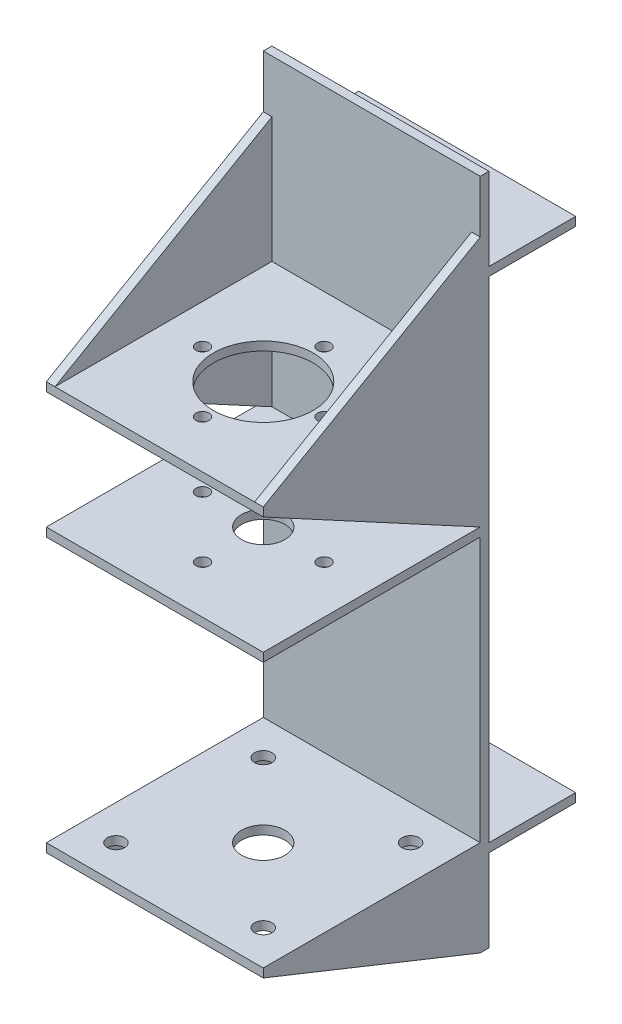
SolidWorks part; units mm, degrees
ref_plane "Front Plane" through (0, 0, 0) normal (0, 0, 1) x (1, 0, 0)
ref_plane "Top Plane" through (0, 0, 0) normal (0, 1, 0) x (1, 0, 0)
ref_plane "Right Plane" through (0, 0, 0) normal (1, 0, 0) x (0, 0, -1)
sketch "Sketch1" plane through (0, 0, 0) normal (0, 0, 1) x (1, 0, 0)
  line L1 (-25, 77.5) -> (25, 77.5)
  line L2 (-25, 77.5) -> (-25, -77.5)
  line L3 (-25, -77.5) -> (25, -77.5)
  line L4 (25, 77.5) -> (25, -77.5)
  line L5 (-25, 77.5) -> (25, -77.5) construction
  line L6 (-25, -77.5) -> (25, 77.5) construction
  point P0 (0, 0)
  point P5 (0, 0)
  point P7 (0, 0)
  dimension "D1" = 155
  dimension "D2" = 50
extrude "Boss-Extrude1" add sketch "Sketch1" along normal blind 2
sketch "Sketch2" plane through (0, 0, 2) normal (0, 0, 1) x (1, 0, 0)
  line L0 (-25, 77.5) -> (-25, -77.5) construction
  line L1 (-25, -57.5) -> (25, -57.5)
  line L2 (-25, -57.5) -> (-25, -55.5)
  line L3 (-25, -55.5) -> (25, -55.5)
  line L4 (25, -57.5) -> (25, -55.5)
  line L5 (25, -77.5) -> (25, 77.5) construction
  line L6 (-25, -77.5) -> (25, -77.5) construction
  dimension "D1" = 2
  dimension "D2" = 20
extrude "Boss-Extrude2" add sketch "Sketch2" along normal blind 50
sketch "Sketch3" plane through (0, 0, 2) normal (0, 0, 1) x (1, 0, 0)
  line L0 (-25, 77.5) -> (-25, -55.5) construction
  line L1 (-25, 5.5) -> (25, 5.5)
  line L2 (-25, 5.5) -> (-25, 7.5)
  line L3 (-25, 7.5) -> (25, 7.5)
  line L4 (25, 5.5) -> (25, 7.5)
  line L5 (25, -55.5) -> (25, 77.5) construction
  line L6 (25, 77.5) -> (-25, 77.5) construction
  dimension "D1" = 2
  dimension "D2" = 70
extrude "Boss-Extrude3" add sketch "Sketch3" along normal blind 50
sketch "Sketch4" plane through (0, -55.5, 0) normal (0, 1, 0) x (1, 0, 0)
  line L0 (-25, -52) -> (25, -2) construction
  line L1 (25, -52) -> (-25, -2) construction
  circle A1 centre (0, -27) radius 24 construction
  circle A2 centre (-16.9706, -43.9706) radius 2
  circle A3 centre (16.9706, -43.9706) radius 2
  circle A4 centre (16.9706, -10.0294) radius 2
  circle A5 centre (-16.9706, -10.0294) radius 2
  dimension "D1" = 48
  dimension "D2" = 4
extrude "Cut-Extrude1" cut sketch "Sketch4" against normal through all
ref_plane "Plane1" through (13.5, 0, 13.5) normal (0.7071, 0, 0.7071) x (0.7071, 0, -0.7071)
ref_plane "Plane2" through (-13.5, 0, 13.5) normal (-0.7071, 0, 0.7071) x (0.7071, 0, 0.7071)
ref_axis "Axis1" through (0, -94.7939, 27) along (0, 1, 0)
sketch "Sketch5" plane through (0, 7.5, 0) normal (0, 1, 0) x (1, 0, 0)
  circle A0 centre (0, -27) radius 5
  dimension "D1" = 10
extrude "Cut-Extrude2" cut sketch "Sketch5" against normal through all
sketch "Sketch6" plane through (0, 5.5, 0) normal (0, -1, 0) x (1, 0, 0)
  circle A0 centre (0, 27) radius 14 construction
  circle A1 centre (0, 41) radius 1.5
  circle A2 centre (14, 27) radius 1.5
  circle A3 centre (0, 13) radius 1.5
  circle A4 centre (-14, 27) radius 1.5
  dimension "D1" = 28
  dimension "D2" = 3
extrude "Cut-Extrude3" cut sketch "Sketch6" against normal through all
sketch "Sketch7" plane through (0, 0, 2) normal (0, 0, 1) x (1, 0, 0)
  line L0 (-25, 77.5) -> (-25, 7.5) construction
  line L1 (-25, 34.5) -> (25, 34.5)
  line L2 (-25, 34.5) -> (-25, 36.5)
  line L3 (-25, 36.5) -> (25, 36.5)
  line L4 (25, 34.5) -> (25, 36.5)
  line L5 (25, 7.5) -> (25, 77.5) construction
  line L6 (25, 77.5) -> (-25, 77.5) construction
  dimension "D1" = 2
  dimension "D2" = 41
extrude "Boss-Extrude4" add sketch "Sketch7" along normal blind 50
sketch "Sketch9" plane through (0, 36.5, 0) normal (0, 1, 0) x (1, 0, 0)
  circle A0 centre (0, -27) radius 11.5
  circle A1 centre (0, -27) radius 14 construction
  circle A2 centre (-14, -27) radius 1.5
  circle A3 centre (0, -41) radius 1.5
  circle A4 centre (14, -27) radius 1.5
  circle A5 centre (0, -13) radius 1.5
  dimension "D1" = 23
  dimension "D2" = 28
  dimension "D3" = 3
extrude "Cut-Extrude5" cut sketch "Sketch9" against normal up to next
sketch "Sketch12" plane through (-25, 0, 0) normal (-1, 0, 0) x (0, 0, 1)
  line L0 (2, 65.3675) -> (52, 36.5)
  line L1 (52, 36.5) -> (2, 36.5)
  line L2 (2, 36.5) -> (2, 65.3675)
  line L3 (2, -77.5) -> (2, -57.5)
  line L4 (2, -57.5) -> (52, -57.5)
  line L5 (52, -57.5) -> (2, -77.5)
  line L6 (2, 77.5) -> (2, 36.5) construction
  line L7 (2, 34.5) -> (52, 34.5)
  line L8 (52, 34.5) -> (2, 7.5)
  line L9 (2, 7.5) -> (2, 34.5)
  line L10 (52, 36.5) -> (2, 36.5) construction
  point P10 (2, 48.4986)
  point P14 (2, 60.0331)
  point P17 (2, 65.2603)
  point P18 (52, 36.5)
  dimension "D1" = 30
extrude "Boss-Extrude5" add sketch "Sketch12" against normal blind 2
mirror "Mirror1" about plane through (0, 0, 0) normal (1, 0, 0) of "Boss-Extrude5"
sketch "Sketch13" plane through (0, 0, 0) normal (0, 0, -1) x (-1, 0, 0)
  line L0 (-25, 58.5) -> (25, 58.5)
  line L1 (25, 58.5) -> (25, 56.5)
  line L2 (25, 77.5) -> (25, -77.5) construction
  line L3 (25, 56.5) -> (1, 56.5)
  line L4 (1, 56.5) -> (1, -56.5)
  line L5 (1, -56.5) -> (25, -56.5)
  line L6 (25, -56.5) -> (25, -58.5)
  line L7 (25, -58.5) -> (-25, -58.5)
  line L8 (-25, -58.5) -> (-25, -56.5)
  line L9 (-25, -77.5) -> (-25, 77.5) construction
  line L10 (-25, -56.5) -> (-1, -56.5)
  line L11 (-1, -56.5) -> (-1, 56.5)
  line L12 (-1, 56.5) -> (-25, 56.5)
  line L13 (-25, 56.5) -> (-25, 58.5)
  line L14 (25, -77.5) -> (-25, -77.5) construction
  line L15 (-25, 77.5) -> (25, 77.5) construction
  point P4 (0, 0)
  point P21 (0, 0)
  point P22 (0, 0)
  point P23 (0, 0)
  point P24 (0, 0)
  point P27 (0, 0)
  point P28 (0, 0)
  point P29 (0, 0)
  point P30 (0, 0)
  point P31 (0, 0)
  dimension "D1" = 2
  dimension "D2" = 2
  dimension "D3" = 2
  dimension "D4" = 19
  dimension "D5" = 19
extrude "Boss-Extrude6" add sketch "Sketch13" along normal blind 20
